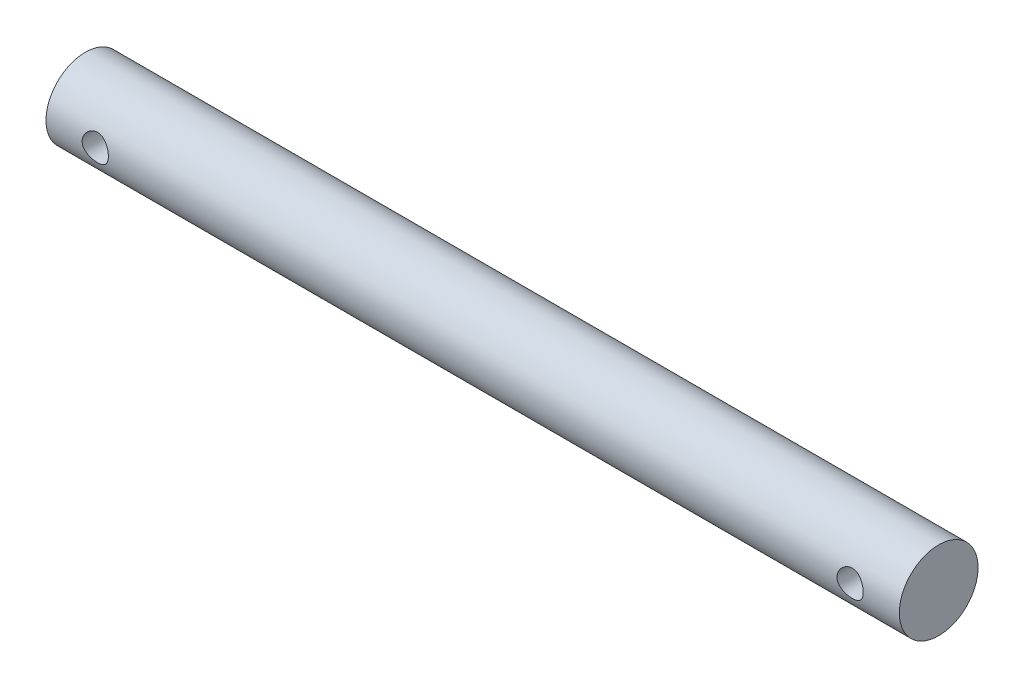
SolidWorks part; units mm, degrees
ref_plane "Front Plane" through (0, 0, 0) normal (0, 0, 1) x (1, 0, 0)
ref_plane "Top Plane" through (0, 0, 0) normal (0, 1, 0) x (1, 0, 0)
ref_plane "Right Plane" through (0, 0, 0) normal (1, 0, 0) x (0, 0, -1)
sketch "Sketch1" plane through (0, 0, 0) normal (0, 0, 1) x (1, 0, 0)
  line L0 (0, 0) -> (130, 0) construction
  line L1 (0, 0) -> (0, 6)
  line L2 (0, 6) -> (130, 6)
  line L3 (130, 6) -> (130, 0)
  line L4 (0, 0) -> (130, 0)
  dimension "D1" = 6
  dimension "D2" = 130
revolve "Revolve1" add sketch "Sketch1" angle 360 about L0 other way angle 360
sketch "Sketch2" plane through (0, 0, 0) normal (0, 0, 1) x (1, 0, 0)
  circle A0 centre (7.5, 0) radius 2
  circle A1 centre (122.5, 0) radius 2
extrude "Cut-Extrude6" cut sketch "Sketch2" against normal through all and the other way through all contours A0
extrude "Cut-Extrude7" cut sketch "Sketch2<7>" against normal through all both and the other way through all contours A1
sketch "Sketch2<7>" plane through (0, 0, 0) normal (0, 0, 1) x (1, 0, 0) same geometry as "Sketch2"
